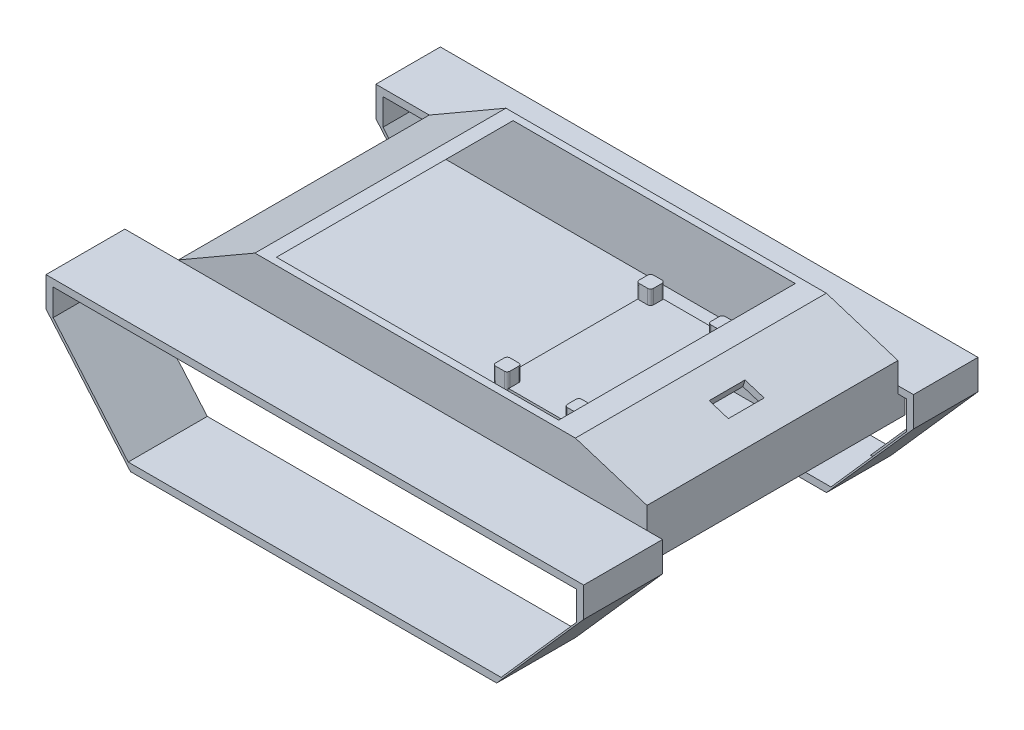
SolidWorks part; units mm, degrees
ref_plane "Front Plane" through (0, 0, 0) normal (0, 0, 1) x (1, 0, 0)
ref_plane "Top Plane" through (0, 0, 0) normal (0, 1, 0) x (1, 0, 0)
ref_plane "Right Plane" through (0, 0, 0) normal (1, 0, 0) x (0, 0, -1)
sketch "Esquisse1" plane through (0, 0, 0) normal (0, 0, 1) x (1, 0, 0)
  line L9 (-177.5, -12.8516) -> (177.5, -12.8516)
  line L10 (-177.5, -12.8516) -> (-177.5, 0)
  line L11 (-95.8817, 47.1484) -> (127.5781, 47.1484)
  line L16 (177.5, -12.8516) -> (177.5, 31.4527)
  line L17 (177.5, 31.4527) -> (127.5781, 47.1484)
  line L18 (-177.5, 0) -> (-95.8817, 47.1484)
  point P0 (0, 0)
  dimension "D1" = 355
extrude "Boss.-Extru.1" add sketch "Esquisse1" along normal blind 175
shell "Coque1" thickness 5
sketch "Esquisse3" plane through (0, 0, 175) normal (0, 0, 1) x (1, 0, 0)
  line L6 (0, 0) -> (0, -81.3544) construction
  line L7 (127.6782, -73.2662) -> (-127.6782, -73.2662)
  line L8 (-127.6782, -73.2662) -> (-186.6066, -4.5164)
  line L9 (-186.6066, -4.5164) -> (-186.6066, 16.2818)
  line L10 (-186.6066, 16.2818) -> (167.5416, 16.2818)
  line L11 (188.3398, 16.2818) -> (167.5416, 16.2818)
  line L12 (188.3398, 16.2818) -> (188.3398, -4.5164)
  line L13 (188.3398, -4.5164) -> (127.6782, -73.2662)
extrude "Boss.-Extru.3" add sketch "Esquisse3" along normal blind 55 and the other way blind 220
sketch "Esquisse4" plane through (-186.6066, 0, 0) normal (-1, 0, 0) x (0, 0, 1)
  line L0 (-45, 16.2818) -> (230, 16.2818) construction
  line L2 (0, 16.2818) -> (0, -73.2662)
  line L3 (0, -73.2662) -> (174.8468, -73.2662)
  line L4 (174.8468, 16.2818) -> (174.8468, -73.2662)
  line L5 (-45, -73.2662) -> (230, -73.2662) construction
  line L7 (0, -73.2662) -> (174.8468, -73.2662)
  line L8 (0, -73.2662) -> (0, 9.0942)
  line L9 (0, 9.0942) -> (174.8468, 9.0942)
  line L10 (174.8468, -73.2662) -> (174.8468, 9.0942)
  line M5 (-45, -4.5164) -> (230, -4.5164)
extrude "Enlèv. mat.-Extru.2" cut sketch "Esquisse4" against normal blind 440 contours L4 L2 L3 M5
sketch "Esquisse5" plane through (0, 16.2818, 0) normal (0, 1, 0) x (1, 0, 0)
  line L0 (188.3398, 45) -> (188.3398, -230) construction
  line L1 (177.5, -175) -> (188.3398, -175)
  line L2 (177.5, -175) -> (177.5, 0)
  line L3 (177.5, 0) -> (188.3398, 0)
  line L4 (188.3398, -175) -> (188.3398, 0)
  line L5 (-186.6066, 45) -> (-186.6066, -230) construction
  line L6 (-149.3146, -175) -> (-186.6066, -175)
  line L7 (-149.3146, -175) -> (-149.3146, 0)
  line L8 (-149.3146, 0) -> (-186.6066, 0)
  line L9 (-186.6066, -175) -> (-186.6066, 0)
extrude "Enlèv. mat.-Extru.3" cut sketch "Esquisse5" against normal blind 440
shell "Coque2" thickness 5
sketch "Esquisse6" plane through (0, 16.2818, 0) normal (0, 1, 0) x (1, 0, 0)
  line L0 (-139.3188, -170) -> (172.5, -170) construction
  line L1 (172.5, -5) -> (-147.8861, -5)
  line L2 (172.5, -5) -> (172.5, -170)
  line L3 (172.5, -170) -> (-147.8861, -170)
  line L4 (-147.8861, -5) -> (-147.8861, -170)
  line L6 (-139.3188, -5) -> (-139.3188, -170) construction
  dimension "D1" = 8.5673
extrude "Boss.-Extru.4" add sketch "Esquisse6" against normal blind 17
sketch "Esquisse8" plane through (-144.3146, 0, 0) normal (1, 0, 0) x (0, 0, -1)
  line L0 (-170, 0.4836) -> (-179.8468, 0.4836) construction
  line L1 (-180, 11.2818) -> (-170, 11.2818)
  line L2 (-180, 11.2818) -> (-180, 0.4836)
  line L3 (-180, 0.4836) -> (-170, 0.4836)
  line L4 (-170, 11.2818) -> (-170, 0.4836)
extrude "Boss.-Extru.5" add sketch "Esquisse8" along normal blind 322
sketch "Esquisse9" plane through (172.5, 0, 0) normal (-1, 0, 0) x (0, 0, 1)
  line L1 (-5, 11.2818) -> (5, 11.2818)
  line L2 (-5, 11.2818) -> (-5, 0.4836)
  line L3 (-5, 0.4836) -> (5, 0.4836)
  line L4 (5, 11.2818) -> (5, 0.4836)
extrude "Boss.-Extru.6" add sketch "Esquisse9" along normal blind 322
sketch "Esquisse10" plane through (0, 16.2818, 0) normal (0, 1, 0) x (1, 0, 0)
  line L0 (-139.3188, -170) -> (172.5, -170) construction
  line L1 (172.5, -5) -> (-139.3188, -5)
  line L2 (172.5, -5) -> (172.5, -170)
  line L3 (172.5, -170) -> (-139.3188, -170)
  line L4 (-139.3188, -5) -> (-139.3188, -170)
extrude "Enlèv. mat.-Extru.5" cut sketch "Esquisse10" against normal blind 16
sketch "Esquisse12" plane through (24.9669, 79.41, 0) normal (0.2999, 0.954, 0) x (0.954, -0.2999, 0)
  line L0 (107.5633, -87.5) -> (159.8945, -87.5) construction
  line L1 (107.5633, -175) -> (107.5633, 0) construction
  line L2 (159.8945, -175) -> (159.8945, 0) construction
  line L4 (140.7289, -100) -> (126.7289, -100)
  line L5 (140.7289, -100) -> (140.7289, -75)
  line L6 (140.7289, -75) -> (126.7289, -75)
  line L7 (126.7289, -100) -> (126.7289, -75)
  line L8 (140.7289, -100) -> (126.7289, -75) construction
  line L9 (140.7289, -75) -> (126.7289, -100) construction
  point P6 (133.7289, -87.5)
  dimension "D1" = 14
  dimension "D2" = 25
extrude "Enlèv. mat.-Extru.7" cut sketch "Esquisse12" against normal blind 10
sketch "Esquisse13" plane through (0, 0.2818, 0) normal (0, 1, 0) x (1, 0, 0)
  line L0 (172.5, -87.5) -> (-157.821, -87.5) construction
  line L1 (172.5, -170) -> (172.5, -5) construction
  line L3 (172.5, -5) -> (102.5, -5)
  line L4 (172.5, -5) -> (172.5, -45)
  line L5 (172.5, -45) -> (102.5, -45)
  line L6 (102.5, -5) -> (102.5, -45)
  line L7 (172.5, -170) -> (102.5, -170)
  line L8 (172.5, -170) -> (172.5, -130)
  line L9 (172.5, -130) -> (102.5, -130)
  line L10 (102.5, -170) -> (102.5, -130)
  dimension "D1" = 70
  dimension "D2" = 40
  dimension "D3" = 70
  dimension "D4" = 40
extrude "Boss.-Extru.7" add sketch "Esquisse13" along normal blind 30
sketch "Esquisse14" plane through (0, 0.2818, 0) normal (0, 1, 0) x (1, 0, 0)
  line L0 (-149.3146, -87.5) -> (177.5, -87.5) construction
  line L1 (-149.3146, 0) -> (-149.3146, -175) construction
  line L2 (177.5, -175) -> (177.5, 0) construction
  line L3 (102.5, -130) -> (102.5, -170) construction
  line L4 (37.5, -32.5) -> (97.5, -32.5)
  line L5 (37.5, -32.5) -> (37.5, -142.5)
  line L6 (37.5, -142.5) -> (97.5, -142.5)
  line L7 (97.5, -32.5) -> (97.5, -142.5)
  line L8 (37.5, -32.5) -> (97.5, -142.5) construction
  line L9 (37.5, -142.5) -> (97.5, -32.5) construction
  point P6 (67.5, -87.5)
  dimension "D1" = 110
  dimension "D2" = 60
  dimension "D3" = 5
extrude "Boss.-Extru.8" add sketch "Esquisse14" along normal blind 30
sketch "Esquisse15" plane through (37.5, 0, 0) normal (-1, 0, 0) x (0, 0, 1)
  line L0 (32.5, 0.2818) -> (142.5, 0.2818) construction
  line L1 (42.5, 0.2818) -> (132.5, 0.2818)
  line L2 (42.5, 0.2818) -> (42.5, 10.2818)
  line L3 (42.5, 10.2818) -> (132.5, 10.2818)
  line L4 (132.5, 0.2818) -> (132.5, 10.2818)
  line L5 (32.5, 30.2818) -> (142.5, 30.2818) construction
  line L6 (42.5, 30.2818) -> (132.5, 30.2818)
  line L7 (42.5, 30.2818) -> (42.5, 20.2818)
  line L8 (42.5, 20.2818) -> (132.5, 20.2818)
  line L9 (132.5, 30.2818) -> (132.5, 20.2818)
  line L10 (32.5, 30.2818) -> (32.5, 0.2818) construction
  line L11 (142.5, 30.2818) -> (142.5, 0.2818) construction
  dimension "D1" = 10
  dimension "D2" = 10
  dimension "D3" = 10
  dimension "D4" = 10
  dimension "D5" = 10
  dimension "D6" = 10
extrude "Enlèv. mat.-Extru.8" cut sketch "Esquisse15" against normal blind 64
sketch "Esquisse16" plane through (0, 0, 32.5) normal (0, 0, -1) x (-1, 0, 0)
  line L0 (-97.5, 30.2818) -> (-37.5, 30.2818) construction
  line L1 (-87.5, 0) -> (-47.5, 0)
  line L2 (-87.5, 0) -> (-87.5, 10)
  line L3 (-87.5, 10) -> (-47.5, 10)
  line L4 (-47.5, 0) -> (-47.5, 10)
  line L5 (-87.5, 30.2818) -> (-47.5, 30.2818)
  line L6 (-87.5, 30.2818) -> (-87.5, 20.2818)
  line L7 (-87.5, 20.2818) -> (-47.5, 20.2818)
  line L8 (-47.5, 30.2818) -> (-47.5, 20.2818)
  line L9 (-37.5, 30.2818) -> (-37.5, 0.2818) construction
  line L10 (-97.5, 30.2818) -> (-97.5, 0.2818) construction
  dimension "D1" = 10
  dimension "D2" = 10
  dimension "D3" = 10
  dimension "D4" = 10
  dimension "D5" = 10
  dimension "D6" = 10
extrude "Enlèv. mat.-Extru.9" cut sketch "Esquisse16" against normal blind 118
sketch "Esquisse17" plane through (37.5, 0, 0) normal (-1, 0, 0) x (0, 0, 1)
  line L1 (42.5, 20.2818) -> (132.5, 20.2818)
  line L2 (42.5, 20.2818) -> (42.5, 10.2818)
  line L3 (42.5, 10.2818) -> (132.5, 10.2818)
  line L4 (132.5, 20.2818) -> (132.5, 10.2818)
extrude "Enlèv. mat.-Extru.10" cut sketch "Esquisse17" against normal blind 1
sketch "Esquisse18" plane through (0, 0, 32.5) normal (0, 0, -1) x (-1, 0, 0)
  line L1 (-87.5, 20.2818) -> (-47.5, 20.2818)
  line L2 (-87.5, 20.2818) -> (-87.5, 10)
  line L3 (-87.5, 10) -> (-47.5, 10)
  line L4 (-47.5, 20.2818) -> (-47.5, 10)
extrude "Enlèv. mat.-Extru.11" cut sketch "Esquisse18" against normal blind 1
sketch "Esquisse19" plane through (97.5, 0, 0) normal (1, 0, 0) x (0, 0, -1)
  line L1 (-132.5, 20.2818) -> (-42.5, 20.2818)
  line L2 (-132.5, 20.2818) -> (-132.5, 10.2818)
  line L3 (-132.5, 10.2818) -> (-42.5, 10.2818)
  line L4 (-42.5, 20.2818) -> (-42.5, 10.2818)
extrude "Enlèv. mat.-Extru.12" cut sketch "Esquisse19" against normal blind 1
sketch "Esquisse20" plane through (0, 0, 142.5) normal (0, 0, 1) x (1, 0, 0)
  line L1 (47.5, 20.2818) -> (87.5, 20.2818)
  line L2 (47.5, 20.2818) -> (47.5, 10)
  line L3 (47.5, 10) -> (87.5, 10)
  line L4 (87.5, 20.2818) -> (87.5, 10)
extrude "Enlèv. mat.-Extru.13" cut sketch "Esquisse20" against normal blind 1
fillet "Congé1" radius 2 20 edges at (87.5, 5.1409, 132.5) (87.5, 25.2818, 132.5) (87.5, 15.2818, 142.5) (97.5, 15.2818, 142.5) (97.5, 15.2818, 132.5) (47.5, 15.2818, 142.5) (37.5, 15.2818, 142.5) (47.5, 5.1409, 132.5) (47.5, 25.2818, 132.5) (37.5, 15.2818, 132.5) (47.5, 5.1409, 42.5) (87.5, 5.1409, 42.5) (37.5, 15.2818, 42.5) (47.5, 25.2818, 42.5) (37.5, 15.2818, 32.5) (47.5, 15.2818, 32.5) (87.5, 15.2818, 32.5) (97.5, 15.2818, 32.5) (87.5, 25.2818, 42.5) (97.5, 15.2818, 42.5)
sketch "Esquisse22" plane through (0, 0, 0) normal (0, 0, 1) x (1, 0, 0)
  line L0 (-181.6066, 11.2818) -> (-149.5, 11.2818)
  line L1 (-149.5, 11.2818) -> (-149.5, -4.5164)
  line L2 (-149.5, -4.5164) -> (175.9635, -4.5164)
  line L3 (177.5, -3.91) -> (177.5, 11.2818)
  line L4 (177.5, 11.2818) -> (183.3398, 11.2818)
  line L5 (183.3398, 11.2818) -> (183.3398, -8.7182)
  line L6 (183.3398, -8.7182) -> (130.7974, -68.2662)
  line L7 (130.7974, -68.2662) -> (-129.274, -68.2662)
  line L8 (-129.274, -68.2662) -> (-181.6066, -7.2115)
  line L9 (-181.6066, -7.2115) -> (-181.6066, 11.2818)
  line L10 (-149.3146, 16.2818) -> (-186.6066, 16.2818) construction
  line L11 (-186.6066, -4.5164) -> (-186.6066, 16.2818) construction
  line L12 (-149.5, 0.4836) -> (-149.5, 11.2818) construction
  line L13 (177.5, -4.5164) -> (-149.3146, -4.5164) construction
  line L15 (127.6782, -73.2662) -> (-127.6782, -73.2662) construction
  line L16 (-186.6066, -4.5164) -> (-127.6782, -73.2662) construction
  line L17 (127.6782, -73.2662) -> (188.3398, -4.5164) construction
  line L18 (188.3398, -4.5164) -> (188.3398, 16.2818) construction
  line L19 (177.5, -4.5164) -> (177.5, 16.2818) construction
  line L20 (188.3398, 16.2818) -> (177.5, 16.2818) construction
  arc A0 (175.9635, -4.5164) -> (177.5, -3.91) centre (175.9635, -2.2668) ccw
  dimension "D1" = 5
  dimension "D2" = 5
  dimension "D3" = 0
  dimension "D4" = 0
  dimension "D5" = 5
  dimension "D6" = 360
  dimension "D7" = 2.0424
  dimension "D8" = 0
  dimension "D9" = 5
  dimension "D10" = 0
  dimension "D11" = 5
  dimension "D12" = 20
extrude "Enlèv. mat.-Extru.14" cut sketch "Esquisse22" against normal blind 33 and the other way blind 307
